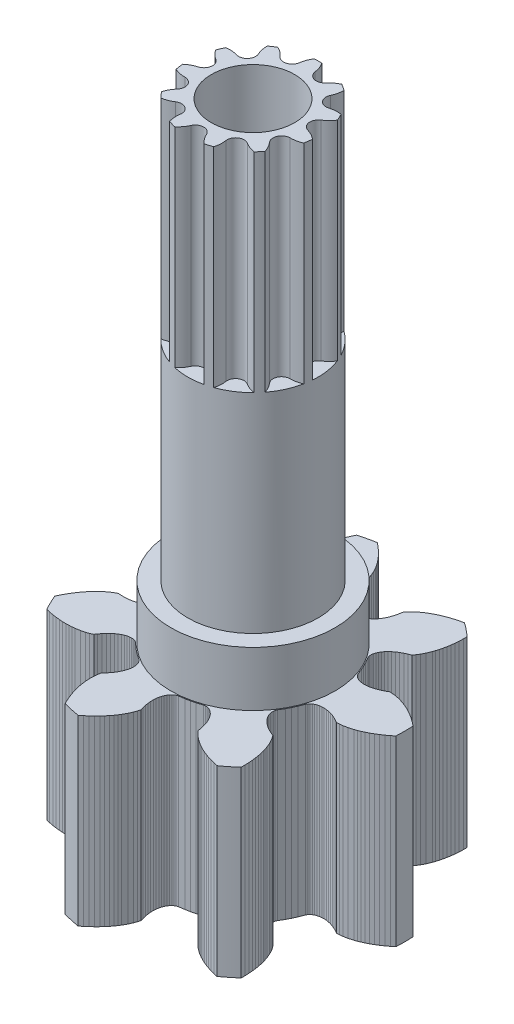
SolidWorks part; units mm, degrees
ref_plane "Front Plane" through (0, 0, 0) normal (0, 0, 1) x (1, 0, 0)
ref_plane "Top Plane" through (0, 0, 0) normal (0, 1, 0) x (1, 0, 0)
ref_plane "Right Plane" through (0, 0, 0) normal (1, 0, 0) x (0, 0, -1)
sketch "Sketch1" plane through (0, 0, 0) normal (0, 1, 0) x (1, 0, 0)
  circle A0 centre (0, 0) radius 3.15
  dimension "D1" = 6.3
extrude "Boss-Extrude1" add sketch "Sketch1" along normal blind 2.1
sketch "Sketch2" plane through (0, 2.1, 0) normal (0, 1, 0) x (1, 0, 0)
  circle A0 centre (0, 0) radius 2.5
  dimension "D1" = 5
extrude "Boss-Extrude3" add sketch "Sketch2" along normal blind 16
sketch "Sketch4" plane through (0, 0, 0) normal (0, -1, 0) x (1, 0, 0)
  line L420 (-1.6777, -5.4575) -> (-1.7402, -5.3144)
  line L421 (-1.7402, -5.3144) -> (-1.7939, -5.1757)
  line L422 (-1.7939, -5.1757) -> (-1.8392, -5.0423)
  line L423 (-1.8392, -5.0423) -> (-1.8764, -4.916)
  line L424 (-1.8764, -4.916) -> (-1.9071, -4.7932)
  line L425 (-1.9071, -4.7932) -> (-1.9311, -4.676)
  line L426 (-1.9311, -4.676) -> (-1.9488, -4.5668)
  line L427 (-1.9488, -4.5668) -> (-1.961, -4.464)
  line L428 (-1.961, -4.464) -> (-1.9715, -4.2798)
  line L429 (-1.9715, -4.2798) -> (-1.9674, -4.1246)
  line L430 (-1.9674, -4.1246) -> (-1.9537, -4.0009)
  line L431 (-1.9537, -4.0009) -> (-1.9303, -3.8867)
  line L432 (-1.9303, -3.8867) -> (-1.8594, -3.8097)
  line L433 (-1.8594, -3.8097) -> (-1.7784, -3.7125)
  line L434 (-1.7784, -3.7125) -> (-1.7087, -3.6155)
  line L435 (-1.7087, -3.6155) -> (-1.6501, -3.5195)
  line L436 (-1.6501, -3.5195) -> (-1.6023, -3.4251)
  line L437 (-1.6023, -3.4251) -> (-1.5652, -3.3333)
  line L438 (-1.5652, -3.3333) -> (-1.5384, -3.2446)
  line L439 (-1.5384, -3.2446) -> (-1.5215, -3.1597)
  line L440 (-1.5215, -3.1597) -> (-1.5143, -3.0795)
  line L441 (-1.5143, -3.0795) -> (-1.5162, -3.0043)
  line L442 (-1.5162, -3.0043) -> (-1.5269, -2.935)
  line L443 (-1.5269, -2.935) -> (-1.5457, -2.8721)
  line L444 (-1.5457, -2.8721) -> (-1.5723, -2.8162)
  line L445 (-1.5723, -2.8162) -> (-1.606, -2.7677)
  line L446 (-1.606, -2.7677) -> (-1.6572, -2.7183)
  line L447 (-1.6572, -2.7183) -> (-1.8447, -2.5928)
  line L448 (-1.8447, -2.5928) -> (-1.984, -2.4878)
  line L449 (-1.984, -2.4878) -> (-2.1173, -2.3754)
  line L450 (-2.1173, -2.3754) -> (-2.2814, -2.2205)
  line L451 (-2.2814, -2.2205) -> (-2.341, -2.1815)
  line L452 (-2.341, -2.1815) -> (-2.3957, -2.1595)
  line L453 (-2.3957, -2.1595) -> (-2.4562, -2.146)
  line L454 (-2.4562, -2.146) -> (-2.5217, -2.1417)
  line L455 (-2.5217, -2.1417) -> (-2.5917, -2.1467)
  line L456 (-2.5917, -2.1467) -> (-2.6653, -2.1615)
  line L457 (-2.6653, -2.1615) -> (-2.742, -2.1865)
  line L458 (-2.742, -2.1865) -> (-2.8209, -2.2218)
  line L459 (-2.8209, -2.2218) -> (-2.9014, -2.2676)
  line L460 (-2.9014, -2.2676) -> (-2.9827, -2.3243)
  line L461 (-2.9827, -2.3243) -> (-3.0641, -2.3918)
  line L462 (-3.0641, -2.3918) -> (-3.1447, -2.4703)
  line L463 (-3.1447, -2.4703) -> (-3.2237, -2.5599)
  line L464 (-3.2237, -2.5599) -> (-3.3005, -2.6605)
  line L465 (-3.3005, -2.6605) -> (-3.3598, -2.7467)
  line L466 (-3.3598, -2.7467) -> (-3.4659, -2.795)
  line L467 (-3.4659, -2.795) -> (-3.5835, -2.8358)
  line L468 (-3.5835, -2.8358) -> (-3.7338, -2.8744)
  line L469 (-3.7338, -2.8744) -> (-3.9158, -2.9052)
  line L470 (-3.9158, -2.9052) -> (-4.0187, -2.9161)
  line L471 (-4.0187, -2.9161) -> (-4.1291, -2.9232)
  line L472 (-4.1291, -2.9232) -> (-4.2487, -2.9258)
  line L473 (-4.2487, -2.9258) -> (-4.3752, -2.9233)
  line L474 (-4.3752, -2.9233) -> (-4.5067, -2.9151)
  line L475 (-4.5067, -2.9151) -> (-4.6468, -2.9006)
  line L476 (-4.6468, -2.9006) -> (-4.794, -2.8791)
  line L477 (-4.794, -2.8791) -> (-4.9474, -2.85)
  line L478 (-4.9474, -2.85) -> (-5.0902, -2.8167)
  line L479 (-5.3759, -2.2235) -> (-5.3129, -2.0911)
  line L480 (-5.3129, -2.0911) -> (-5.2399, -1.953)
  line L481 (-5.2399, -1.953) -> (-5.165, -1.8245)
  line L482 (-5.165, -1.8245) -> (-5.089, -1.7059)
  line L483 (-5.089, -1.7059) -> (-5.0134, -1.5981)
  line L484 (-5.0134, -1.5981) -> (-4.9365, -1.4976)
  line L485 (-4.9365, -1.4976) -> (-4.8599, -1.4057)
  line L486 (-4.8599, -1.4057) -> (-4.7855, -1.3238)
  line L487 (-4.7855, -1.3238) -> (-4.7128, -1.2502)
  line L488 (-4.7128, -1.2502) -> (-4.5753, -1.1271)
  line L489 (-4.5753, -1.1271) -> (-4.4514, -1.0336)
  line L490 (-4.4514, -1.0336) -> (-4.3462, -0.9671)
  line L491 (-4.3462, -0.9671) -> (-4.2422, -0.9142)
  line L492 (-4.2422, -0.9142) -> (-4.1379, -0.9217)
  line L493 (-4.1379, -0.9217) -> (-4.0114, -0.9244)
  line L494 (-4.0114, -0.9244) -> (-3.8921, -0.9184)
  line L495 (-3.8921, -0.9184) -> (-3.7804, -0.9043)
  line L496 (-3.7804, -0.9043) -> (-3.6769, -0.8828)
  line L497 (-3.6769, -0.8828) -> (-3.5819, -0.8546)
  line L498 (-3.5819, -0.8546) -> (-3.4959, -0.8203)
  line L499 (-3.4959, -0.8203) -> (-3.4191, -0.7805)
  line L500 (-3.4191, -0.7805) -> (-3.3518, -0.7361)
  line L501 (-3.3518, -0.7361) -> (-3.2942, -0.6878)
  line L502 (-3.2942, -0.6878) -> (-3.2467, -0.6363)
  line L503 (-3.2467, -0.6363) -> (-3.2093, -0.5823)
  line L504 (-3.2093, -0.5823) -> (-3.1821, -0.5267)
  line L505 (-3.1821, -0.5267) -> (-3.1652, -0.4701)
  line L506 (-3.1652, -0.4701) -> (-3.1585, -0.3992)
  line L507 (-3.1585, -0.3992) -> (-3.1773, -0.1744)
  line L508 (-3.1773, -0.1744) -> (-3.1821, 0)
  line L509 (-3.1821, 0) -> (-3.1773, 0.1743)
  line L510 (-3.1773, 0.1743) -> (-3.1585, 0.3991)
  line L511 (-3.1585, 0.3991) -> (-3.1652, 0.47)
  line L512 (-3.1652, 0.47) -> (-3.1821, 0.5266)
  line L513 (-3.1821, 0.5266) -> (-3.2093, 0.5822)
  line L514 (-3.2093, 0.5822) -> (-3.2467, 0.6362)
  line L515 (-3.2467, 0.6362) -> (-3.2942, 0.6877)
  line L516 (-3.2942, 0.6877) -> (-3.3518, 0.7361)
  line L517 (-3.3518, 0.7361) -> (-3.4191, 0.7805)
  line L518 (-3.4191, 0.7805) -> (-3.4959, 0.8202)
  line L519 (-3.4959, 0.8202) -> (-3.5819, 0.8545)
  line L520 (-3.5819, 0.8545) -> (-3.6769, 0.8828)
  line L521 (-3.6769, 0.8828) -> (-3.7804, 0.9043)
  line L522 (-3.7804, 0.9043) -> (-3.8921, 0.9183)
  line L523 (-3.8921, 0.9183) -> (-4.0114, 0.9243)
  line L524 (-4.0114, 0.9243) -> (-4.1379, 0.9216)
  line L525 (-4.1379, 0.9216) -> (-4.2422, 0.9142)
  line L526 (-4.2422, 0.9142) -> (-4.3462, 0.967)
  line L527 (-4.3462, 0.967) -> (-4.4514, 1.0335)
  line L528 (-4.4514, 1.0335) -> (-4.5753, 1.127)
  line L529 (-4.5753, 1.127) -> (-4.7128, 1.2501)
  line L530 (-4.7128, 1.2501) -> (-4.7855, 1.3238)
  line L531 (-4.7855, 1.3238) -> (-4.8599, 1.4056)
  line L532 (-4.8599, 1.4056) -> (-4.9365, 1.4975)
  line L533 (-4.9365, 1.4975) -> (-5.0134, 1.598)
  line L534 (-5.0134, 1.598) -> (-5.089, 1.7059)
  line L535 (-5.089, 1.7059) -> (-5.165, 1.8244)
  line L536 (-5.165, 1.8244) -> (-5.2399, 1.9529)
  line L537 (-5.2399, 1.9529) -> (-5.3129, 2.0911)
  line L538 (-5.3129, 2.0911) -> (-5.3759, 2.2234)
  line L539 (-5.0902, 2.8167) -> (-4.9474, 2.8499)
  line L540 (-4.9474, 2.8499) -> (-4.794, 2.879)
  line L541 (-4.794, 2.879) -> (-4.6468, 2.9005)
  line L542 (-4.6468, 2.9005) -> (-4.5067, 2.9151)
  line L543 (-4.5067, 2.9151) -> (-4.3752, 2.9232)
  line L544 (-4.3752, 2.9232) -> (-4.2487, 2.9257)
  line L545 (-4.2487, 2.9257) -> (-4.1291, 2.9231)
  line L546 (-4.1291, 2.9231) -> (-4.0187, 2.916)
  line L547 (-4.0187, 2.916) -> (-3.9158, 2.9051)
  line L548 (-3.9158, 2.9051) -> (-3.7338, 2.8743)
  line L549 (-3.7338, 2.8743) -> (-3.5835, 2.8358)
  line L550 (-3.5835, 2.8358) -> (-3.4659, 2.7949)
  line L551 (-3.4659, 2.7949) -> (-3.3598, 2.7466)
  line L552 (-3.3598, 2.7466) -> (-3.3005, 2.6604)
  line L553 (-3.3005, 2.6604) -> (-3.2237, 2.5598)
  line L554 (-3.2237, 2.5598) -> (-3.1447, 2.4703)
  line L555 (-3.1447, 2.4703) -> (-3.0641, 2.3918)
  line L556 (-3.0641, 2.3918) -> (-2.9827, 2.3242)
  line L557 (-2.9827, 2.3242) -> (-2.9014, 2.2676)
  line L558 (-2.9014, 2.2676) -> (-2.8209, 2.2217)
  line L559 (-2.8209, 2.2217) -> (-2.742, 2.1864)
  line L560 (-2.742, 2.1864) -> (-2.6653, 2.1615)
  line L561 (-2.6653, 2.1615) -> (-2.5917, 2.1466)
  line L562 (-2.5917, 2.1466) -> (-2.5217, 2.1416)
  line L563 (-2.5217, 2.1416) -> (-2.4562, 2.146)
  line L564 (-2.4562, 2.146) -> (-2.3957, 2.1594)
  line L565 (-2.3957, 2.1594) -> (-2.341, 2.1815)
  line L566 (-2.341, 2.1815) -> (-2.2814, 2.2205)
  line L567 (-2.2814, 2.2205) -> (-2.1173, 2.3753)
  line L568 (-2.1173, 2.3753) -> (-1.984, 2.4878)
  line L569 (-1.984, 2.4878) -> (-1.8447, 2.5927)
  line L570 (-1.8447, 2.5927) -> (-1.6572, 2.7182)
  line L571 (-1.6572, 2.7182) -> (-1.606, 2.7676)
  line L572 (-1.606, 2.7676) -> (-1.5723, 2.8161)
  line L573 (-1.5723, 2.8161) -> (-1.5457, 2.8721)
  line L574 (-1.5457, 2.8721) -> (-1.5269, 2.935)
  line L575 (-1.5269, 2.935) -> (-1.5162, 3.0043)
  line L576 (-1.5162, 3.0043) -> (-1.5143, 3.0794)
  line L577 (-1.5143, 3.0794) -> (-1.5215, 3.1597)
  line L578 (-1.5215, 3.1597) -> (-1.5384, 3.2445)
  line L579 (-1.5384, 3.2445) -> (-1.5652, 3.3332)
  line L580 (-1.5652, 3.3332) -> (-1.6023, 3.4251)
  line L581 (-1.6023, 3.4251) -> (-1.6501, 3.5194)
  line L582 (-1.6501, 3.5194) -> (-1.7087, 3.6154)
  line L583 (-1.7087, 3.6154) -> (-1.7784, 3.7125)
  line L584 (-1.7784, 3.7125) -> (-1.8594, 3.8097)
  line L585 (-1.8594, 3.8097) -> (-1.9303, 3.8866)
  line L586 (-1.9303, 3.8866) -> (-1.9537, 4.0009)
  line L587 (-1.9537, 4.0009) -> (-1.9674, 4.1246)
  line L588 (-1.9674, 4.1246) -> (-1.9715, 4.2797)
  line L589 (-1.9715, 4.2797) -> (-1.961, 4.464)
  line L590 (-1.961, 4.464) -> (-1.9488, 4.5668)
  line L591 (-1.9488, 4.5668) -> (-1.9311, 4.6759)
  line L592 (-1.9311, 4.6759) -> (-1.9071, 4.7932)
  line L593 (-1.9071, 4.7932) -> (-1.8764, 4.9159)
  line L594 (-1.8764, 4.9159) -> (-1.8392, 5.0423)
  line L595 (-1.8392, 5.0423) -> (-1.7939, 5.1756)
  line L596 (-1.7939, 5.1756) -> (-1.7402, 5.3143)
  line L597 (-1.7402, 5.3143) -> (-1.6777, 5.4575)
  line L598 (-1.6777, 5.4575) -> (-1.6135, 5.5893)
  line L599 (-0.9715, 5.7358) -> (-0.8565, 5.6449)
  line L600 (-0.8565, 5.6449) -> (-0.7381, 5.543)
  line L601 (-0.7381, 5.543) -> (-0.6295, 5.4414)
  line L602 (-0.6295, 5.4414) -> (-0.5308, 5.3409)
  line L603 (-0.5308, 5.3409) -> (-0.4425, 5.2432)
  line L604 (-0.4425, 5.2432) -> (-0.3616, 5.1459)
  line L605 (-0.3616, 5.1459) -> (-0.2891, 5.0507)
  line L606 (-0.2891, 5.0507) -> (-0.2258, 4.96)
  line L607 (-0.2258, 4.96) -> (-0.1702, 4.8727)
  line L608 (-0.1702, 4.8727) -> (-0.0808, 4.7113)
  line L609 (-0.0808, 4.7113) -> (-0.0172, 4.5697)
  line L610 (-0.0172, 4.5697) -> (0.0242, 4.4523)
  line L611 (0.0242, 4.4523) -> (0.0526, 4.3392)
  line L612 (0.0526, 4.3392) -> (0.0222, 4.2391)
  line L613 (0.0222, 4.2391) -> (-0.0086, 4.1164)
  line L614 (-0.0086, 4.1164) -> (-0.0293, 3.9987)
  line L615 (-0.0293, 3.9987) -> (-0.0405, 3.8868)
  line L616 (-0.0405, 3.8868) -> (-0.0426, 3.7811)
  line L617 (-0.0426, 3.7811) -> (-0.0362, 3.6822)
  line L618 (-0.0362, 3.6822) -> (-0.0218, 3.5907)
  line L619 (-0.0218, 3.5907) -> (-0.0002, 3.5069)
  line L620 (-0.0002, 3.5069) -> (0.0281, 3.4314)
  line L621 (0.0281, 3.4314) -> (0.0624, 3.3646)
  line L622 (0.0624, 3.3646) -> (0.1021, 3.3068)
  line L623 (0.1021, 3.3068) -> (0.1464, 3.2583)
  line L624 (0.1464, 3.2583) -> (0.1946, 3.2194)
  line L625 (0.1946, 3.2194) -> (0.246, 3.1903)
  line L626 (0.246, 3.1903) -> (0.3136, 3.1681)
  line L627 (0.3136, 3.1681) -> (0.537, 3.1363)
  line L628 (0.537, 3.1363) -> (0.708, 3.1022)
  line L629 (0.708, 3.1022) -> (0.8769, 3.0588)
  line L630 (0.8769, 3.0588) -> (1.0919, 2.9904)
  line L631 (1.0919, 2.9904) -> (1.1625, 2.9811)
  line L632 (1.1625, 2.9811) -> (1.2214, 2.985)
  line L633 (1.2214, 2.985) -> (1.2817, 2.9991)
  line L634 (1.2817, 2.9991) -> (1.3427, 3.0236)
  line L635 (1.3427, 3.0236) -> (1.4035, 3.0585)
  line L636 (1.4035, 3.0585) -> (1.4634, 3.1038)
  line L637 (1.4634, 3.1038) -> (1.5217, 3.1596)
  line L638 (1.5217, 3.1596) -> (1.5775, 3.2256)
  line L639 (1.5775, 3.2256) -> (1.6301, 3.3019)
  line L640 (1.6301, 3.3019) -> (1.6788, 3.3882)
  line L641 (1.6788, 3.3882) -> (1.7228, 3.4843)
  line L642 (1.7228, 3.4843) -> (1.7613, 3.59)
  line L643 (1.7613, 3.59) -> (1.7937, 3.705)
  line L644 (1.7937, 3.705) -> (1.8192, 3.829)
  line L645 (1.8192, 3.829) -> (1.8352, 3.9324)
  line L646 (1.8352, 3.9324) -> (1.9099, 4.0219)
  line L647 (1.9099, 4.0219) -> (1.9981, 4.1097)
  line L648 (1.9981, 4.1097) -> (2.1168, 4.2097)
  line L649 (2.1168, 4.2097) -> (2.2674, 4.3164)
  line L650 (2.2674, 4.3164) -> (2.3554, 4.3709)
  line L651 (2.3554, 4.3709) -> (2.4518, 4.4251)
  line L652 (2.4518, 4.4251) -> (2.5584, 4.4794)
  line L653 (2.5584, 4.4794) -> (2.6735, 4.532)
  line L654 (2.6735, 4.532) -> (2.7955, 4.5817)
  line L655 (2.7955, 4.5817) -> (2.928, 4.6294)
  line L656 (2.928, 4.6294) -> (3.0699, 4.6739)
  line L657 (3.0699, 4.6739) -> (3.2208, 4.7143)
  line L658 (3.2208, 4.7143) -> (3.3639, 4.7463)
  line L659 (3.8787, 4.3357) -> (3.8793, 4.1891)
  line L660 (3.8793, 4.1891) -> (3.8735, 4.033)
  line L661 (3.8735, 4.033) -> (3.8618, 3.8847)
  line L662 (3.8618, 3.8847) -> (3.8448, 3.7449)
  line L663 (3.8448, 3.7449) -> (3.8234, 3.615)
  line L664 (3.8234, 3.615) -> (3.7978, 3.4911)
  line L665 (3.7978, 3.4911) -> (3.7686, 3.375)
  line L666 (3.7686, 3.375) -> (3.7371, 3.269)
  line L667 (3.7371, 3.269) -> (3.7036, 3.1711)
  line L668 (3.7036, 3.1711) -> (3.6331, 3.0005)
  line L669 (3.6331, 3.0005) -> (3.562, 2.8625)
  line L670 (3.562, 2.8625) -> (3.4961, 2.757)
  line L671 (3.4961, 2.757) -> (3.4253, 2.6643)
  line L672 (3.4253, 2.6643) -> (3.3281, 2.6257)
  line L673 (3.3281, 2.6257) -> (3.213, 2.5732)
  line L674 (3.213, 2.5732) -> (3.1081, 2.516)
  line L675 (3.1081, 2.516) -> (3.0136, 2.4549)
  line L676 (3.0136, 2.4549) -> (2.9296, 2.3907)
  line L677 (2.9296, 2.3907) -> (2.8563, 2.324)
  line L678 (2.8563, 2.324) -> (2.7937, 2.2557)
  line L679 (2.7937, 2.2557) -> (2.7417, 2.1866)
  line L680 (2.7417, 2.1866) -> (2.7003, 2.1174)
  line L681 (2.7003, 2.1174) -> (2.6695, 2.0489)
  line L682 (2.6695, 2.0489) -> (2.649, 1.9819)
  line L683 (2.649, 1.9819) -> (2.6387, 1.917)
  line L684 (2.6387, 1.917) -> (2.6383, 1.8551)
  line L685 (2.6383, 1.8551) -> (2.6476, 1.7967)
  line L686 (2.6476, 1.7967) -> (2.6724, 1.73)
  line L687 (2.6724, 1.73) -> (2.7869, 1.5356)
  line L688 (2.7869, 1.5356) -> (2.8668, 1.3806)
  line L689 (2.8668, 1.3806) -> (2.9382, 1.2215)
  line L690 (2.9382, 1.2215) -> (3.0188, 1.0107)
  line L691 (3.0188, 1.0107) -> (3.0555, 0.9498)
  line L692 (3.0555, 0.9498) -> (3.0953, 0.9061)
  line L693 (3.0953, 0.9061) -> (3.144, 0.8678)
  line L694 (3.144, 0.8678) -> (3.2011, 0.8354)
  line L695 (3.2011, 0.8354) -> (3.2663, 0.8096)
  line L696 (3.2663, 0.8096) -> (3.3391, 0.791)
  line L697 (3.3391, 0.791) -> (3.419, 0.7802)
  line L698 (3.419, 0.7802) -> (3.5054, 0.7777)
  line L699 (3.5054, 0.7777) -> (3.5979, 0.7842)
  line L700 (3.5979, 0.7842) -> (3.6957, 0.7999)
  line L701 (3.6957, 0.7999) -> (3.7983, 0.8255)
  line L702 (3.7983, 0.8255) -> (3.905, 0.8612)
  line L703 (3.905, 0.8612) -> (4.0151, 0.9076)
  line L704 (4.0151, 0.9076) -> (4.1279, 0.9649)
  line L705 (4.1279, 0.9649) -> (4.2187, 1.0169)
  line L706 (4.2187, 1.0169) -> (4.3353, 1.0144)
  line L707 (4.3353, 1.0144) -> (4.4589, 1.0001)
  line L708 (4.4589, 1.0001) -> (4.6111, 0.9696)
  line L709 (4.6111, 0.9696) -> (4.7884, 0.9184)
  line L710 (4.7884, 0.9184) -> (4.8859, 0.8836)
  line L711 (4.8859, 0.8836) -> (4.9884, 0.8421)
  line L712 (4.9884, 0.8421) -> (5.0973, 0.7926)
  line L713 (5.0973, 0.7926) -> (5.2102, 0.7354)
  line L714 (5.2102, 0.7354) -> (5.3251, 0.671)
  line L715 (5.3251, 0.671) -> (5.445, 0.5972)
  line L716 (5.445, 0.5972) -> (5.5683, 0.5139)
  line L717 (5.5683, 0.5139) -> (5.6939, 0.4211)
  line L718 (5.6939, 0.4211) -> (5.8081, 0.3292)
  line L719 (5.8081, -0.3293) -> (5.6939, -0.4212)
  line L720 (5.6939, -0.4212) -> (5.5683, -0.514)
  line L721 (5.5683, -0.514) -> (5.445, -0.5972)
  line L722 (5.445, -0.5972) -> (5.3251, -0.6711)
  line L723 (5.3251, -0.6711) -> (5.2102, -0.7354)
  line L724 (5.2102, -0.7354) -> (5.0973, -0.7926)
  line L725 (5.0973, -0.7926) -> (4.9884, -0.8421)
  line L726 (4.9884, -0.8421) -> (4.8859, -0.8837)
  line L727 (4.8859, -0.8837) -> (4.7884, -0.9185)
  line L728 (4.7884, -0.9185) -> (4.6111, -0.9697)
  line L729 (4.6111, -0.9697) -> (4.4589, -1.0002)
  line L730 (4.4589, -1.0002) -> (4.3353, -1.0144)
  line L731 (4.3353, -1.0144) -> (4.2187, -1.017)
  line L732 (4.2187, -1.017) -> (4.1279, -0.965)
  line L733 (4.1279, -0.965) -> (4.0151, -0.9077)
  line L734 (4.0151, -0.9077) -> (3.905, -0.8613)
  line L735 (3.905, -0.8613) -> (3.7983, -0.8255)
  line L736 (3.7983, -0.8255) -> (3.6957, -0.8)
  line L737 (3.6957, -0.8) -> (3.5979, -0.7842)
  line L738 (3.5979, -0.7842) -> (3.5054, -0.7778)
  line L739 (3.5054, -0.7778) -> (3.419, -0.7803)
  line L740 (3.419, -0.7803) -> (3.3391, -0.7911)
  line L741 (3.3391, -0.7911) -> (3.2663, -0.8097)
  line L742 (3.2663, -0.8097) -> (3.2011, -0.8354)
  line L743 (3.2011, -0.8354) -> (3.144, -0.8678)
  line L744 (3.144, -0.8678) -> (3.0953, -0.9062)
  line L745 (3.0953, -0.9062) -> (3.0555, -0.9498)
  line L746 (3.0555, -0.9498) -> (3.0188, -1.0108)
  line L747 (3.0188, -1.0108) -> (2.9382, -1.2215)
  line L748 (2.9382, -1.2215) -> (2.8668, -1.3806)
  line L749 (2.8668, -1.3806) -> (2.7869, -1.5356)
  line L750 (2.7869, -1.5356) -> (2.6724, -1.7301)
  line L751 (2.6724, -1.7301) -> (2.6476, -1.7968)
  line L752 (2.6476, -1.7968) -> (2.6383, -1.8551)
  line L753 (2.6383, -1.8551) -> (2.6387, -1.9171)
  line L754 (2.6387, -1.9171) -> (2.649, -1.9819)
  line L755 (2.649, -1.9819) -> (2.6695, -2.049)
  line L756 (2.6695, -2.049) -> (2.7003, -2.1175)
  line L757 (2.7003, -2.1175) -> (2.7417, -2.1867)
  line L758 (2.7417, -2.1867) -> (2.7937, -2.2558)
  line L759 (2.7937, -2.2558) -> (2.8563, -2.3241)
  line L760 (2.8563, -2.3241) -> (2.9296, -2.3907)
  line L761 (2.9296, -2.3907) -> (3.0136, -2.455)
  line L762 (3.0136, -2.455) -> (3.1081, -2.5161)
  line L763 (3.1081, -2.5161) -> (3.213, -2.5733)
  line L764 (3.213, -2.5733) -> (3.3281, -2.6257)
  line L765 (3.3281, -2.6257) -> (3.4253, -2.6643)
  line L766 (3.4253, -2.6643) -> (3.4961, -2.757)
  line L767 (3.4961, -2.757) -> (3.562, -2.8626)
  line L768 (3.562, -2.8626) -> (3.6331, -3.0006)
  line L769 (3.6331, -3.0006) -> (3.7036, -3.1711)
  line L770 (3.7036, -3.1711) -> (3.7371, -3.2691)
  line L771 (3.7371, -3.2691) -> (3.7686, -3.3751)
  line L772 (3.7686, -3.3751) -> (3.7978, -3.4911)
  line L773 (3.7978, -3.4911) -> (3.8234, -3.615)
  line L774 (3.8234, -3.615) -> (3.8448, -3.745)
  line L775 (3.8448, -3.745) -> (3.8618, -3.8848)
  line L776 (3.8618, -3.8848) -> (3.8735, -4.0331)
  line L777 (3.8735, -4.0331) -> (3.8793, -4.1892)
  line L778 (3.8793, -4.1892) -> (3.8787, -4.3358)
  line L779 (3.3639, -4.7463) -> (3.2208, -4.7143)
  line L780 (3.2208, -4.7143) -> (3.0699, -4.6739)
  line L781 (3.0699, -4.6739) -> (2.928, -4.6295)
  line L782 (2.928, -4.6295) -> (2.7955, -4.5818)
  line L783 (2.7955, -4.5818) -> (2.6735, -4.5321)
  line L784 (2.6735, -4.5321) -> (2.5584, -4.4795)
  line L785 (2.5584, -4.4795) -> (2.4518, -4.4252)
  line L786 (2.4518, -4.4252) -> (2.3554, -4.3709)
  line L787 (2.3554, -4.3709) -> (2.2674, -4.3164)
  line L788 (2.2674, -4.3164) -> (2.1168, -4.2097)
  line L789 (2.1168, -4.2097) -> (1.9981, -4.1098)
  line L790 (1.9981, -4.1098) -> (1.9099, -4.022)
  line L791 (1.9099, -4.022) -> (1.8352, -3.9324)
  line L792 (1.8352, -3.9324) -> (1.8192, -3.829)
  line L793 (1.8192, -3.829) -> (1.7937, -3.7051)
  line L794 (1.7937, -3.7051) -> (1.7613, -3.5901)
  line L795 (1.7613, -3.5901) -> (1.7228, -3.4844)
  line L796 (1.7228, -3.4844) -> (1.6788, -3.3883)
  line L797 (1.6788, -3.3883) -> (1.6301, -3.3019)
  line L798 (1.6301, -3.3019) -> (1.5775, -3.2257)
  line L799 (1.5775, -3.2257) -> (1.5217, -3.1596)
  line L800 (1.5217, -3.1596) -> (1.4634, -3.1039)
  line L801 (1.4634, -3.1039) -> (1.4035, -3.0586)
  line L802 (1.4035, -3.0586) -> (1.3427, -3.0237)
  line L803 (1.3427, -3.0237) -> (1.2817, -2.9992)
  line L804 (1.2817, -2.9992) -> (1.2214, -2.9851)
  line L805 (1.2214, -2.9851) -> (1.1625, -2.9812)
  line L806 (1.1625, -2.9812) -> (1.0919, -2.9905)
  line L807 (1.0919, -2.9905) -> (0.8769, -3.0588)
  line L808 (0.8769, -3.0588) -> (0.708, -3.1023)
  line L809 (0.708, -3.1023) -> (0.537, -3.1364)
  line L810 (0.537, -3.1364) -> (0.3136, -3.1681)
  line L811 (0.3136, -3.1681) -> (0.246, -3.1904)
  line L812 (0.246, -3.1904) -> (0.1946, -3.2194)
  line L813 (0.1946, -3.2194) -> (0.1464, -3.2583)
  line L814 (0.1464, -3.2583) -> (0.1021, -3.3068)
  line L815 (0.1021, -3.3068) -> (0.0624, -3.3647)
  line L816 (0.0624, -3.3647) -> (0.0281, -3.4315)
  line L817 (0.0281, -3.4315) -> (-0.0002, -3.507)
  line L818 (-0.0002, -3.507) -> (-0.0218, -3.5907)
  line L819 (-0.0218, -3.5907) -> (-0.0362, -3.6823)
  line L820 (-0.0362, -3.6823) -> (-0.0426, -3.7811)
  line L821 (-0.0426, -3.7811) -> (-0.0405, -3.8868)
  line L822 (-0.0405, -3.8868) -> (-0.0293, -3.9988)
  line L823 (-0.0293, -3.9988) -> (-0.0086, -4.1165)
  line L824 (-0.0086, -4.1165) -> (0.0222, -4.2392)
  line L825 (0.0222, -4.2392) -> (0.0526, -4.3393)
  line L826 (0.0526, -4.3393) -> (0.0242, -4.4524)
  line L827 (0.0242, -4.4524) -> (-0.0172, -4.5698)
  line L828 (-0.0172, -4.5698) -> (-0.0808, -4.7113)
  line L829 (-0.0808, -4.7113) -> (-0.1702, -4.8728)
  line L830 (-0.1702, -4.8728) -> (-0.2258, -4.9601)
  line L831 (-0.2258, -4.9601) -> (-0.2891, -5.0508)
  line L832 (-0.2891, -5.0508) -> (-0.3616, -5.146)
  line L833 (-0.3616, -5.146) -> (-0.4425, -5.2433)
  line L834 (-0.4425, -5.2433) -> (-0.5308, -5.341)
  line L835 (-0.5308, -5.341) -> (-0.6295, -5.4414)
  line L836 (-0.6295, -5.4414) -> (-0.7381, -5.5431)
  line L837 (-0.7381, -5.5431) -> (-0.8565, -5.645)
  line L838 (-0.8565, -5.645) -> (-0.9715, -5.7359)
  line L839 (-1.6135, -5.5894) -> (-1.6777, -5.4575)
  arc A7 (-5.3759, -2.2235) -> (-5.0902, -2.8167) centre (0, 0) ccw
  arc A8 (-5.0902, 2.8167) -> (-5.3759, 2.2234) centre (0, -0.0001) ccw
  arc A9 (-0.9715, 5.7358) -> (-1.6135, 5.5893) centre (0, -0.0001) ccw
  arc A10 (3.8787, 4.3357) -> (3.3639, 4.7463) centre (-0.0001, -0.0001) ccw
  arc A11 (5.8081, -0.3293) -> (5.8081, 0.3292) centre (-0.0001, 0) ccw
  arc A12 (3.3639, -4.7463) -> (3.8787, -4.3358) centre (-0.0001, 0) ccw
  arc A13 (-1.6135, -5.5894) -> (-0.9715, -5.7359) centre (0, 0) ccw
extrude "Boss-Extrude4" add sketch "Sketch4" along normal blind 7
sketch "Sketch3" plane through (0, 0, 0) normal (0, -1, 0) x (1, 0, 0)
  circle A0 centre (0, 0) radius 1.1
  circle A1 centre (0, 0) radius 0.75
  dimension "D1" = 2.2
  dimension "D2" = 1.5
extrude "Cut-Extrude2" cut sketch "Sketch3" along normal through all contours A0 A1 | A1 region at (-1.0689, 0, 0) region at (0, 0, 0)
ref_plane "Plane2" through (0, 5.9, 0) normal (0, 1, 0) x (1, 0, 0)
sketch "Sketch6" plane through (0, -7, 0) normal (0, -1, 0) x (1, 0, 0)
  circle A0 centre (0, 0) radius 1.7
  dimension "D1" = 3.4
extrude "Cut-Extrude3" cut sketch "Sketch6" against normal offset from surface (7.6 mm away) 1.5 up to face at (0, 2.1, 2.5)
sketch "Sketch7" plane through (0, 0.6, 0) normal (0, -1, 0) x (1, 0, 0)
  circle A0 centre (0, 0) radius 1.6
  dimension "D1" = 3.2
ref_plane "Plane4" through (0, 8.1, 0) normal (0, 1, 0) x (1, 0, 0)
extrude "Cut-Extrude4" cut sketch "Sketch7" against normal through all
sketch "Sketch8" plane through (0, 18.1, 0) normal (0, 1, 0) x (1, 0, 0)
  arc A0 (-0.8749, -1.9145) -> (-0.8716, -1.8825) centre (-1.1988, -1.8653) ccw
  arc A1 (-0.2845, -2.0549) -> (-0.2991, -2.0836) centre (0, -2.2173) ccw
  arc A2 (0.2845, -2.0549) -> (-0.2845, -2.0549) centre (0, -2.2173) ccw
  arc A3 (0.2991, -2.0836) -> (0.2845, -2.0549) centre (0, -2.2173) ccw
  arc A4 (0.8716, -1.8825) -> (0.8749, -1.9145) centre (1.1988, -1.8653) ccw
  arc A5 (1.3781, -1.5911) -> (1.3503, -1.5748) centre (1.1988, -1.8653) ccw
  arc A6 (2.0195, -0.5935) -> (1.9873, -0.5948) centre (2.0169, -0.9211) ccw
  arc A7 (1.751, -1.1124) -> (1.7711, -1.1376) centre (2.0169, -0.9211) ccw
  arc A8 (2.0744, 0.0108) -> (2.1049, 0.0005) centre (2.1947, 0.3156) ccw
  arc A9 (2.0198, 0.5926) -> (1.9934, 0.574) centre (2.1947, 0.3156) ccw
  arc A10 (2.0195, -0.5935) -> (2.4493, -0.5015) centre (2.0276, 0.4185) ccw
  arc A11 (1.9873, -0.5948) -> (1.751, -1.1124) centre (2.0169, -0.9211) ccw
  arc A12 (1.9829, -1.5226) -> (1.7711, -1.1376) centre (1.0115, -1.8064) ccw
  arc A13 (1.7893, -1.7461) -> (1.9829, -1.5226) centre (0, 0) ccw
  arc A14 (1.3781, -1.5911) -> (1.7893, -1.7461) centre (1.9319, -0.7441) ccw
  arc A15 (1.3503, -1.5748) -> (0.8716, -1.8825) centre (1.1988, -1.8653) ccw
  arc A16 (0.8449, -2.353) -> (0.8749, -1.9145) centre (-0.1257, -2.0665) ccw
  arc A17 (0.5613, -2.4363) -> (0.8449, -2.353) centre (0, 0) ccw
  arc A18 (0.2991, -2.0836) -> (0.5613, -2.4363) centre (1.2229, -1.6705) ccw
  arc A19 (-0.5613, -2.4363) -> (-0.2991, -2.0836) centre (-1.2229, -1.6705) ccw
  arc A20 (-0.8449, -2.353) -> (-0.5613, -2.4363) centre (0, 0) ccw
  arc A21 (-0.8749, -1.9145) -> (-0.8449, -2.353) centre (0.1257, -2.0665) ccw
  arc A22 (2.4493, -0.5015) -> (2.4913, -0.2089) centre (0, 0) ccw
  arc A23 (2.4913, -0.2089) -> (2.1049, 0.0005) centre (1.8275, -0.9727) ccw
  arc A24 (1.9934, 0.574) -> (2.0744, 0.0108) centre (2.1947, 0.3156) ccw
  arc A25 (2.0198, 0.5926) -> (2.3316, 0.9023) centre (1.4794, 1.4482) ccw
  arc A26 (2.3316, 0.9023) -> (2.2088, 1.1712) centre (0, 0) ccw
  arc A27 (-1.3503, -1.5748) -> (-1.3781, -1.5911) centre (-1.1988, -1.8653) ccw
  arc A28 (-1.7711, -1.1376) -> (-1.751, -1.1124) centre (-2.0169, -0.9211) ccw
  arc A29 (-1.9873, -0.5948) -> (-2.0195, -0.5935) centre (-2.0169, -0.9211) ccw
  arc A30 (-2.1049, 0.0005) -> (-2.0744, 0.0108) centre (-2.1947, 0.3156) ccw
  arc A31 (-1.9934, 0.574) -> (-2.0198, 0.5926) centre (-2.1947, 0.3156) ccw
  arc A32 (-0.8716, -1.8825) -> (-1.3503, -1.5748) centre (-1.1988, -1.8653) ccw
  arc A33 (-1.7893, -1.7461) -> (-1.3781, -1.5911) centre (-1.9319, -0.7441) ccw
  arc A34 (-1.9829, -1.5226) -> (-1.7893, -1.7461) centre (0, 0) ccw
  arc A35 (-1.7711, -1.1376) -> (-1.9829, -1.5226) centre (-1.0115, -1.8064) ccw
  arc A36 (-1.751, -1.1124) -> (-1.9873, -0.5948) centre (-2.0169, -0.9211) ccw
  arc A37 (-2.4493, -0.5015) -> (-2.0195, -0.5935) centre (-2.0276, 0.4185) ccw
  arc A38 (-2.4913, -0.2089) -> (-2.4493, -0.5015) centre (0, 0) ccw
  arc A39 (-2.1049, 0.0005) -> (-2.4913, -0.2089) centre (-1.8275, -0.9727) ccw
  arc A40 (-2.0744, 0.0108) -> (-1.9934, 0.574) centre (-2.1947, 0.3156) ccw
  arc A41 (-2.3316, 0.9023) -> (-2.0198, 0.5926) centre (-1.4794, 1.4482) ccw
  arc A42 (-1.7705, 1.1384) -> (-1.7393, 1.1306) centre (-1.6757, 1.452) ccw
  arc A43 (-1.3667, 1.5606) -> (-1.3788, 1.5905) centre (-1.6757, 1.452) ccw
  arc A44 (-0.874, 1.9149) -> (-0.8519, 1.8915) centre (-0.6247, 2.1275) ccw
  arc A45 (-0.306, 2.0518) -> (-0.3001, 2.0834) centre (-0.6247, 2.1275) ccw
  arc A46 (1.7393, 1.1306) -> (1.7705, 1.1384) centre (1.6757, 1.452) ccw
  arc A47 (1.3788, 1.5905) -> (1.3667, 1.5606) centre (1.6757, 1.452) ccw
  arc A48 (2.2088, 1.1712) -> (1.7705, 1.1384) centre (2.0633, 0.1697) ccw
  arc A49 (1.3667, 1.5606) -> (1.7393, 1.1306) centre (1.6757, 1.452) ccw
  arc A50 (1.3788, 1.5905) -> (1.4736, 2.0196) centre (0.4616, 2.0182) ccw
  arc A51 (1.4736, 2.0196) -> (1.2249, 2.1794) centre (0, 0) ccw
  arc A52 (0.8519, 1.8915) -> (0.874, 1.9149) centre (0.6247, 2.1275) ccw
  arc A53 (0.3001, 2.0834) -> (0.306, 2.0518) centre (0.6247, 2.1275) ccw
  arc A54 (1.2249, 2.1794) -> (0.874, 1.9149) centre (1.644, 1.2583) ccw
  arc A55 (0.306, 2.0518) -> (0.8519, 1.8915) centre (0.6247, 2.1275) ccw
  arc A56 (0.3001, 2.0834) -> (0.1478, 2.4957) centre (-0.7028, 1.9474) ccw
  arc A57 (0.1478, 2.4957) -> (0, 2.5001) centre (0, 0) ccw
  arc A58 (0, 2.5001) -> (-0.1478, 2.4957) centre (0, 0) ccw
  arc A59 (-0.1478, 2.4957) -> (-0.3001, 2.0834) centre (0.7028, 1.9474) ccw
  arc A60 (-0.8519, 1.8915) -> (-0.306, 2.0518) centre (-0.6247, 2.1275) ccw
  arc A61 (-0.874, 1.9149) -> (-1.2249, 2.1794) centre (-1.644, 1.2583) ccw
  arc A62 (-1.2249, 2.1794) -> (-1.4736, 2.0196) centre (0, 0) ccw
  arc A63 (-1.4736, 2.0196) -> (-1.3788, 1.5905) centre (-0.4616, 2.0182) ccw
  arc A64 (-1.7393, 1.1306) -> (-1.3667, 1.5606) centre (-1.6757, 1.452) ccw
  arc A65 (-1.7705, 1.1384) -> (-2.2088, 1.1712) centre (-2.0633, 0.1697) ccw
  arc A66 (-2.2088, 1.1712) -> (-2.3316, 0.9023) centre (0, 0) ccw
  circle A68 centre (0, 0) radius 0.7859 construction
  circle A69 centre (0, 0) radius 1.8897 construction
extrude "Cut-Extrude5" cut sketch "Sketch8" against normal blind 8 flip side to cut
